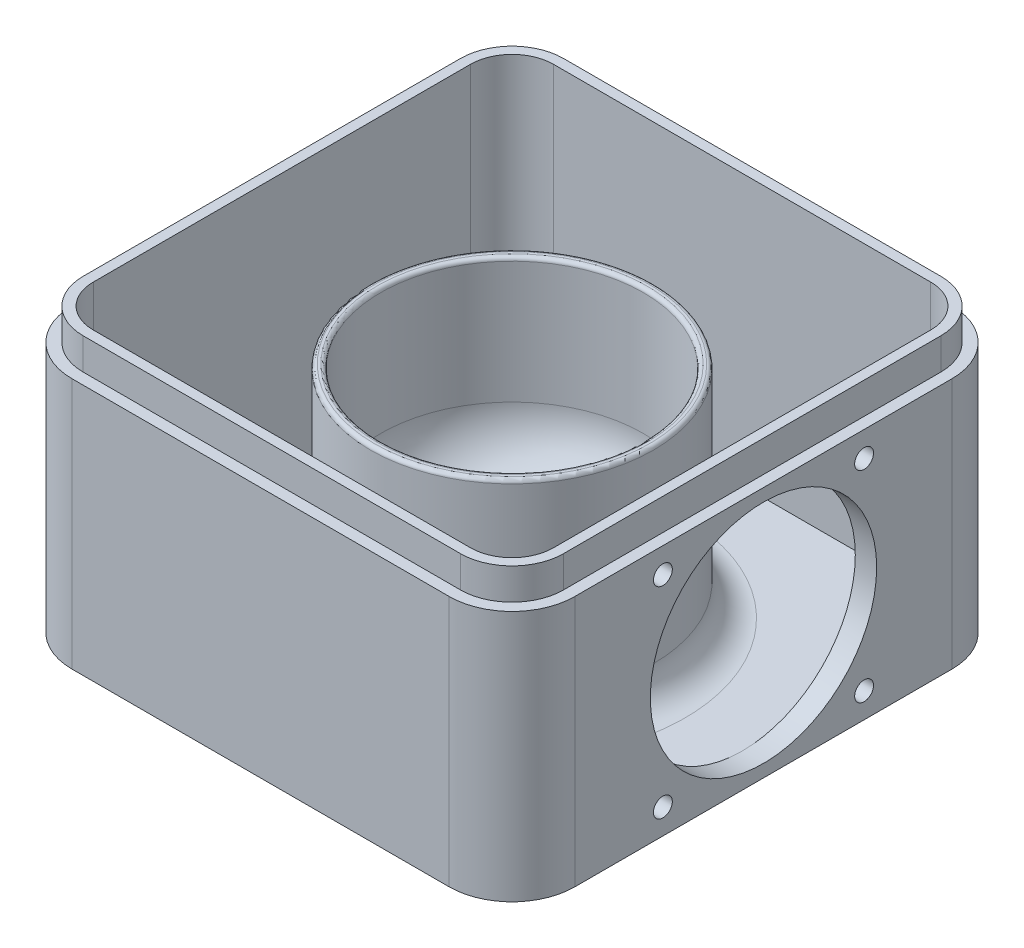
SolidWorks part; units mm, degrees
ref_plane "Спереди" through (0, 0, 0) normal (0, 0, 1) x (1, 0, 0)
ref_plane "Сверху" through (0, 0, 0) normal (0, 1, 0) x (1, 0, 0)
ref_plane "Справа" through (0, 0, 0) normal (1, 0, 0) x (0, 0, -1)
sketch "Sketch1" plane through (0, 0, 0) normal (0, 1, 0) x (1, 0, 0)
  line L1 (-40, -40) -> (40, -40)
  line L2 (-40, -40) -> (-40, 40)
  line L3 (-40, 40) -> (40, 40)
  line L4 (40, -40) -> (40, 40)
  line L5 (-40, -40) -> (40, 40) construction
  line L6 (-40, 40) -> (40, -40) construction
  point P0 (0, 0)
  dimension "D1" = 80
  dimension "D2" = 80
extrude "Boss-Extrude1" add sketch "Sketch1" along normal blind 40
fillet "Fillet1" radius 10 4 edges at (-40, 20, -40) (-40, 20, 40) (40, 20, 40) (40, 20, -40)
sketch3d "3DSketch4"
  line L0 (-38.2, 40, -30) -> (-38.2, 40, 30)
  line L1 (-30, 40, 38.2) -> (30, 40, 38.2)
  line L2 (38.2, 40, 30) -> (38.2, 40, -30)
  line L3 (30, 40, -38.2) -> (-30, 40, -38.2)
  line L4 (-38.2, 40, -30) -> (-38.2, 40, 30)
  line L5 (-30, 40, 38.2) -> (30, 40, 38.2)
  line L6 (38.2, 40, 30) -> (38.2, 40, -30)
  line L7 (30, 40, -38.2) -> (-30, 40, -38.2)
  arc A0 (-38.2, 40, 30) -> (-30, 40, 38.2) centre (-30, 40, 30) ccw
  arc A1 (30, 40, 38.2) -> (38.2, 40, 30) centre (30, 40, 30) ccw
  arc A2 (38.2, 40, -30) -> (30, 40, -38.2) centre (30, 40, -30) ccw
  arc A3 (-30, 40, -38.2) -> (-38.2, 40, -30) centre (-30, 40, -30) ccw
  arc A4 (-38.2, 40, 30) -> (-30, 40, 38.2) centre (-30, 40, 30) ccw
  arc A5 (30, 40, 38.2) -> (38.2, 40, 30) centre (30, 40, 30) ccw
  arc A6 (38.2, 40, -30) -> (30, 40, -38.2) centre (30, 40, -30) ccw
  arc A7 (-30, 40, -38.2) -> (-38.2, 40, -30) centre (-30, 40, -30) ccw
  point P4 (-30, 48.2, 30)
  point P8 (30, 48.2, 30)
  point P12 (30, 48.2, -30)
  point P15 (-30, 48.2, -30)
  point P16 (-30, 48.2, 30)
  point P17 (30, 48.2, 30)
  point P18 (30, 48.2, -30)
  point P19 (-30, 48.2, -30)
  dimension "D1" = 1.8
extrude "Boss-Extrude5" add sketch "3DSketch4" along direction (0, -1, 0) on the side of the normal blind 5
sketch3d "3DSketch5"
  line L0 (-36.6, 45, -30) -> (-36.6, 45, 30)
  line L1 (-30, 45, 36.6) -> (30, 45, 36.6)
  line L2 (36.6, 45, 30) -> (36.6, 45, -30)
  line L3 (30, 45, -36.6) -> (-30, 45, -36.6)
  line L4 (-36.6, 45, -30) -> (-36.6, 45, 30)
  line L5 (-30, 45, 36.6) -> (30, 45, 36.6)
  line L6 (36.6, 45, 30) -> (36.6, 45, -30)
  line L7 (30, 45, -36.6) -> (-30, 45, -36.6)
  arc A0 (-36.6, 45, 30) -> (-30, 45, 36.6) centre (-30, 45, 30) ccw
  arc A1 (30, 45, 36.6) -> (36.6, 45, 30) centre (30, 45, 30) ccw
  arc A2 (36.6, 45, -30) -> (30, 45, -36.6) centre (30, 45, -30) ccw
  arc A3 (-30, 45, -36.6) -> (-36.6, 45, -30) centre (-30, 45, -30) ccw
  arc A4 (-36.6, 45, 30) -> (-30, 45, 36.6) centre (-30, 45, 30) ccw
  arc A5 (30, 45, 36.6) -> (36.6, 45, 30) centre (30, 45, 30) ccw
  arc A6 (36.6, 45, -30) -> (30, 45, -36.6) centre (30, 45, -30) ccw
  arc A7 (-30, 45, -36.6) -> (-36.6, 45, -30) centre (-30, 45, -30) ccw
  point P4 (-30, 51.6, 30)
  point P8 (30, 51.6, 30)
  point P12 (30, 51.6, -30)
  point P15 (-30, 51.6, -30)
  point P16 (-30, 51.6, 30)
  point P17 (30, 51.6, 30)
  point P18 (30, 51.6, -30)
  point P19 (-30, 51.6, -30)
  dimension "D1" = 1.6
extrude "Cut-Extrude6" cut sketch "3DSketch5" along direction (0, -1, 0) on the side against the normal blind 43
sketch "Sketch8" plane through (0, 2, 0) normal (0, 1, 0) x (1, 0, 0)
  circle A0 centre (0, 0) radius 22.5
  dimension "D1" = 45
extrude "Boss-Extrude4" add sketch "Sketch8" along normal blind 35
sketch "Sketch9" plane through (0, 37, 0) normal (0, 1, 0) x (1, 0, 0)
  circle A0 centre (0, 0) radius 20.9
  circle A1 centre (0, 0) radius 22.5 construction
  dimension "D1" = 1.6
extrude "Cut-Extrude5" cut sketch "Sketch9" against normal blind 30
fillet "Fillet2" radius 10 1 edges at (0, 7, 20.9)
sketch "Sketch10" plane through (40, 0, 0) normal (1, 0, 0) x (0, 0, -1)
  line L0 (0, 0) -> (0, 40) construction
  line L5 (-30, 0) -> (30, 0) construction
  line L6 (-30, 40) -> (30, 40) construction
  line L7 (30, 20) -> (-30, 20) construction
  line L8 (30, 0) -> (30, 40) construction
  line L9 (-30, 40) -> (-30, 0) construction
  circle A0 centre (0, 20) radius 18
  circle A1 centre (16, 4) radius 1.5
  circle A2 centre (-16, 4) radius 1.5
  circle A3 centre (-16, 36) radius 1.5
  circle A4 centre (16, 36) radius 1.5
  point P0 (0, 20)
  dimension "D1" = 20
  dimension "D2" = 16
  dimension "D4" = 36
  dimension "D3" = 16
extrude "Cut-Fan" cut sketch "Sketch10" against normal up to next
fillet "Fillet3" radius 5 1 edges at (0, 2, -22.5)
fillet "Fillet5" radius 0.6 2 edges at (0, 37, 20.9) (0, 37, 22.5)
sketch "Sketch12" plane through (0, 2, 0) normal (0, -1, 0) x (1, 0, 0)
  line L1 (-36.6, 22.5) -> (-26.6, 22.5)
  line L2 (-36.6, 22.5) -> (-36.6, -22.5)
  line L3 (-36.6, -22.5) -> (-26.6, -22.5)
  line L4 (-26.6, 22.5) -> (-26.6, -22.5)
  line L9 (-36.6, -30) -> (-36.6, 30) construction
  point P6 (-36.6, 0)
  dimension "D1" = 45
  dimension "D2" = 10
extrude "Cut-Extrude10" cut sketch "Sketch12" along normal blind 8 and the other way blind 8
fillet "Fillet10" radius 5 4 edges at (-36.6, 1, 22.5) (-36.6, 1, -22.5) (-26.6, 1, 22.5) (-26.6, 1, -22.5)
fillet "Fillet9" radius 1 6 edges at (-36.6, 0, 0) (-35.1355, 0, -21.0355) (-28.0645, 0, -21.0355) (-26.6, 0, 0) (-28.0645, 0, 21.0355) (-35.1355, 0, 21.0355)
